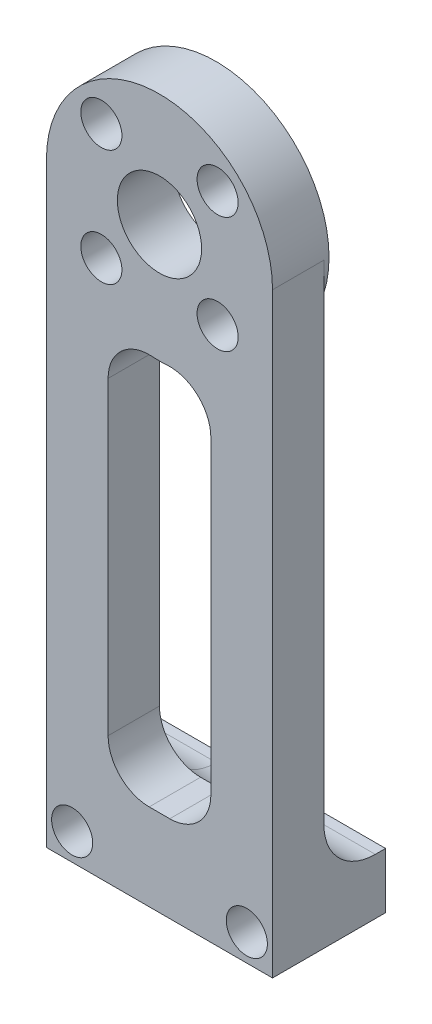
SolidWorks part; units mm, degrees
ref_plane "Front Plane" through (0, 0, 0) normal (0, 0, 1) x (1, 0, 0)
ref_plane "Top Plane" through (0, 0, 0) normal (0, 1, 0) x (1, 0, 0)
ref_plane "Right Plane" through (0, 0, 0) normal (1, 0, 0) x (0, 0, -1)
sketch "Sketch1" plane through (0, 0, 0) normal (0, 0, 1) x (1, 0, 0)
  line L0 (0, 29) -> (0, -29) construction
  line L2 (11, 29) -> (11, -29)
  line L4 (-11, 29) -> (-11, -29)
  line L5 (-11, -29) -> (11, -29)
  line L7 (11, -29) -> (-11, -29)
  line L8 (11, -29) -> (11, -23.58)
  line L9 (11, -23.58) -> (-11, -23.58)
  line L10 (-11, -29) -> (-11, -23.58)
  line L12 (-5, 18.6438) -> (-5, -20.58)
  line L13 (-5, -20.58) -> (5, -20.58)
  line L14 (5, 18.6438) -> (5, -20.58)
  circle A0 centre (0, 29) radius 11
  arc A1 (-5, 18.6438) -> (5, 18.6438) centre (0, 29) ccw
  point P0 (0, 0)
  point P2 (0, 0)
  point P8 (0, -29)
  dimension "D3" = 22
  dimension "D1" = 58
  dimension "D4" = 5.42
  dimension "D5" = 23
  dimension "D7" = 6
  dimension "D2" = 22
  dimension "D6" = 3
  dimension "D8" = 6
extrude "Boss-Extrude1" add sketch "Sketch1" along normal blind 5 contours L2 A0 L4 | A0 | A0 L0 L2 | L8 L7 L10 L9 region at (0, 29, 0) region at (10.43, 2.71, 0)
extrude "Boss-Extrude2" add sketch "Sketch1<3>" against normal blind 0.5 contours A0 region at (0, 29, 0)
sketch "Sketch1<3>" plane through (0, 0, 0) normal (0, 0, 1) x (1, 0, 0) same geometry as "Sketch1"
sketch "Sketch2" plane through (0, 0, 5) normal (0, 0, 1) x (1, 0, 0)
  line L0 (0, 29) -> (5.6569, 34.6569) construction
  line L1 (11, 29) -> (11, -29) construction
  circle A0 centre (0, 29) radius 4.1
  circle A1 centre (5.6569, 34.6569) radius 1.1
  circle A2 centre (5.6569, 34.6569) radius 2
  dimension "D1" = 8.2
  dimension "D2" = 2.2
  dimension "D5" = 4
  dimension "D3" = 8
  dimension "D4" = 45
extrude "Cut-Extrude1" cut sketch "Sketch2" against normal up to surface (5.5 mm away) contours A0 | A1 region at (0, 29, 5) region at (5.6569, 34.6569, 5) up to face at (11, 29, -0.5)
extrude "Cut-Extrude2" cut sketch "Sketch2<3>" against normal offset from surface (4.5 mm away) 1 contours A2 A1 region at (3.7134, 34.6569, 5) up to face at (4.1, 29, -0.5)
sketch "Sketch2<3>" plane through (0, 0, 5) normal (0, 0, 1) x (1, 0, 0) same geometry as "Sketch2"
pattern_circular "CirPattern2" count 4 over 360 about axis through (0, 29, 5) along (0, 0, 1) of "Cut-Extrude2", "Cut-Extrude1"
extrude "Boss-Extrude3" add sketch "Sketch1<6>" against normal blind 6 contours L0 L9 L4 L5 | L9 L0 L7 L2 region at (-5.5, -26.29, 0) region at (5.5, -26.29, 0)
sketch "Sketch1<6>" plane through (0, 0, 0) normal (0, 0, 1) x (1, 0, 0) same geometry as "Sketch1"
sketch "Sketch3" plane through (0, 0, 5) normal (0, 0, 1) x (1, 0, 0)
  line L0 (-8.5, -26.3852) -> (8.5, -26.3852) construction
  line L1 (-11, -29) -> (11, -29) construction
  circle A0 centre (-8.5, -26.3852) radius 1.1
  circle A1 centre (8.5, -26.3852) radius 1.1
  circle A2 centre (-8.5, -26.3852) radius 2
  circle A3 centre (8.5, -26.3852) radius 2
  point P4 (0, -26.3852)
  dimension "D1" = 2.2
  dimension "D4" = 4
  dimension "D2" = 17
  dimension "D3" = 2.6148
extrude "Cut-Extrude3" cut sketch "Sketch3" against normal up to surface (11 mm away) contours A0 | A1 region at (-8.5, -26.3852, 5) region at (8.5, -26.3852, 5) up to face at (0, -26.29, -6)
extrude "Cut-Extrude4" cut sketch "Sketch3<3>" against normal offset from surface (10 mm away) 1 up to face at (-7.4, -26.3852, -6)
sketch "Sketch3<3>" plane through (0, 0, 5) normal (0, 0, 1) x (1, 0, 0) same geometry as "Sketch3"
fillet "Filete1" radius 4 4 edges at (5, 18.6438, 2.5) (-5, 18.6438, 2.5) (5, -20.58, 2.5) (-5, -20.58, 2.5)
fillet "Filete3" radius 5 1 edges at (0, -23.58, 0)
